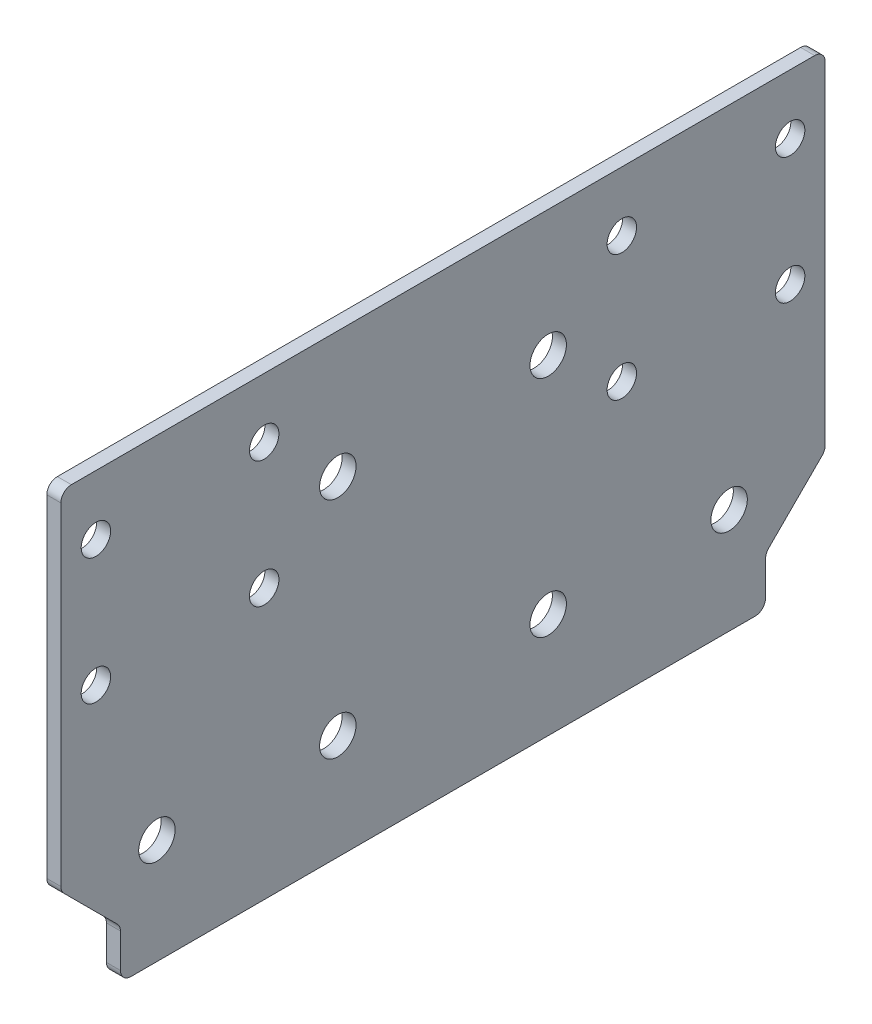
SolidWorks part; units mm, degrees
ref_plane "Front Plane" through (0, 0, 0) normal (0, 0, 1) x (1, 0, 0)
ref_plane "Top Plane" through (0, 0, 0) normal (0, 1, 0) x (1, 0, 0)
ref_plane "Right Plane" through (0, 0, 0) normal (1, 0, 0) x (0, 0, -1)
sketch "Sketch1" plane through (0, 0, 0) normal (1, 0, 0) x (0, 0, -1)
  line L0 (104, 0) -> (104, -35) construction
  line L1 (0, 0) -> (109, 0)
  line L2 (0, 0) -> (0, -35)
  line L3 (0, -35) -> (109, -35)
  line L4 (109, 0) -> (109, -35)
  line L5 (109, -17.5) -> (0, -17.5) construction
  line L6 (92, 0) -> (92, -35) construction
  line L7 (54.5, 0) -> (54.5, -35) construction
  line L8 (17, 0) -> (17, -35) construction
  circle A0 centre (104, -8.5) radius 2.1
  circle A1 centre (104, -26.5) radius 2.1
  circle A2 centre (80, -26.5) radius 2.1
  circle A3 centre (80, -8.5) radius 2.1
  circle A4 centre (5, -26.5) radius 2.1
  circle A5 centre (5, -8.5) radius 2.1
  circle A6 centre (29, -26.5) radius 2.1
  circle A7 centre (29, -8.5) radius 2.1
  point P31 (54.5, -7.21)
  dimension "D3" = 12
  dimension "D4" = 4.2
  dimension "D6" = 18
  dimension "D1" = 75
  dimension "D2" = 35
  dimension "D5" = 17
extrude "Boss-Extrude1" add sketch "Sketch1" along normal blind 2
sketch "Sketch2" plane through (2, 0, 0) normal (1, 0, 0) x (0, 0, -1)
  line L0 (54.5, -35) -> (54.5, -65) construction
  line L1 (0, -35) -> (109, -35) construction
  line L4 (100.5, -65) -> (8.5, -65)
  line L9 (100.5, -65) -> (100.5, -35)
  line L10 (100.5, -35) -> (8.5, -35)
  line L11 (8.5, -65) -> (8.5, -35)
  line L12 (100.5, -65) -> (8.5, -35) construction
  line L13 (100.5, -35) -> (8.5, -65) construction
  point P4 (54.5, -50)
  dimension "D1" = 30
  dimension "D2" = 92
extrude "Boss-Extrude2" add sketch "Sketch2" against normal blind 2
sketch "Sketch3" plane through (2, 0, 0) normal (1, 0, 0) x (0, 0, -1)
  line L0 (0, -50) -> (92, -50) construction
  line L1 (0, 0) -> (0, -35) construction
  line L3 (54.5, -65) -> (54.5, -0.9679) construction
  line L6 (0, 0) -> (0, -35) construction
  line L8 (8.5, -65) -> (100.5, -65) construction
  line L9 (79.5882, -18) -> (29.2397, -18) construction
  line L10 (109, 0) -> (0, 0) construction
  circle A0 centre (13.7, -50) radius 2.6
  circle A1 centre (39.5, -50) radius 2.6
  circle A2 centre (95.3, -50) radius 2.6
  circle A3 centre (69.5, -50) radius 2.6
  circle A4 centre (69.5, -18) radius 2.6
  circle A5 centre (39.5, -18) radius 2.6
  dimension "D1" = 5.2
  dimension "D2" = 5.2
  dimension "D4" = 81.6
  dimension "D5" = 30
  dimension "D7" = 5.2
  dimension "D8" = 30
  dimension "D3" = 54.5
  dimension "D6" = 15
  dimension "D9" = 18
extrude "Cut-Extrude1" cut sketch "Sketch3" against normal through all
chamfer "Chamfer1" distance 23 angle 45 2 edges at (1, -35, -100.5) (1, -35, -8.5)
fillet "Fillet1" radius 1.5 8 edges at (1, 0, 0) (1, -49.5, 0) (1, -58, -8.5) (1, -65, -8.5) (1, -65, -100.5) (1, -58, -100.5) (1, -49.5, -109) (1, 0, -109)
